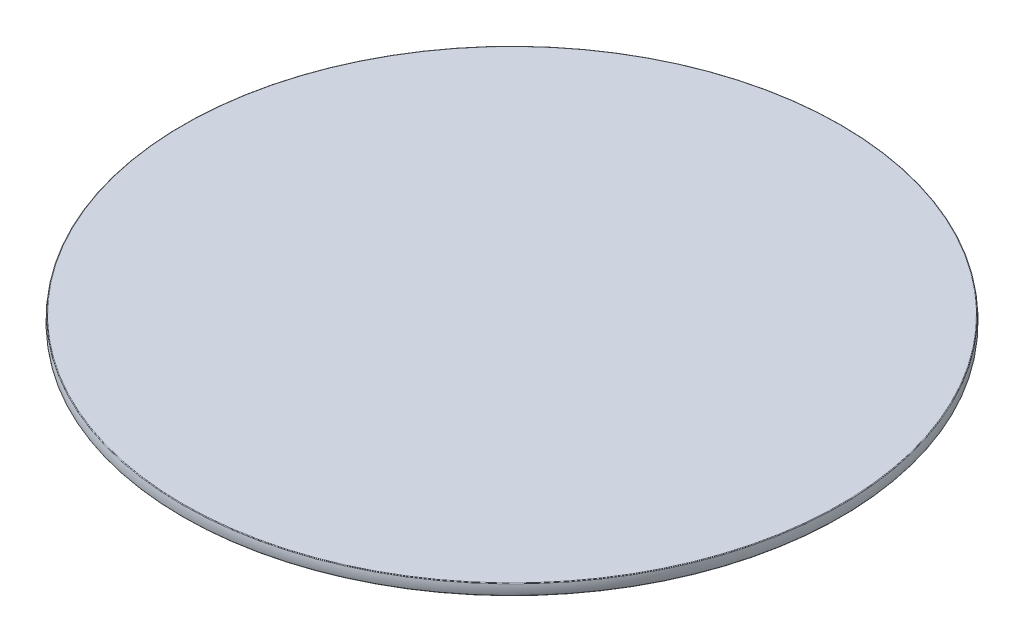
SolidWorks part; units mm, degrees
ref_plane "Front Plane" through (0, 0, 0) normal (0, 0, 1) x (1, 0, 0)
ref_plane "Top Plane" through (0, 0, 0) normal (0, 1, 0) x (1, 0, 0)
ref_plane "Right Plane" through (0, 0, 0) normal (1, 0, 0) x (0, 0, -1)
sketch "Sketch1" plane through (0, 0, 0) normal (0, 1, 0) x (1, 0, 0)
  circle A0 centre (0, 0) radius 150
  dimension "D1" = 300
extrude "Boss-Extrude1" add sketch "Sketch1" along normal blind 5
sketch "Sketch2" plane through (0, 0, 0) normal (0, 0, 1) x (1, 0, 0)
  line L0 (-150, 2.5) -> (-138, 2.5) construction
  line L1 (-150, 5) -> (-150, 0) construction
  line L2 (150, 5) -> (-150, 5) construction
  line L3 (-150, 0) -> (150, 0) construction
  line L4 (-150, 5) -> (-152.2183, 5)
  line L5 (-149.7367, 5) -> (-150, 5)
  line L6 (-150, 0) -> (-149.7367, 0)
  line L7 (0, 0) -> (0, 76.927) construction
  line L8 (-152.2183, 5) -> (-152.2183, 0)
  line L9 (-152.2183, 0) -> (-150, 0)
  arc A0 (-149.7367, 5) -> (-149.7367, 0) centre (-138, 2.5) ccw
  point P7 (-150, 2.5)
  dimension "D1" = 12
revolve "Cut-Revolve2" cut sketch "Sketch2" angle 360 about L7
fillet "Fillet1" radius 0.3 2 edges at (0, 0, -149.7367) (0, 5, -149.7367)
equation "\"GlassPlateDiameter\"=300"
equation "\"D1@Sketch1\"=\"GlassPlateDiameter\""
